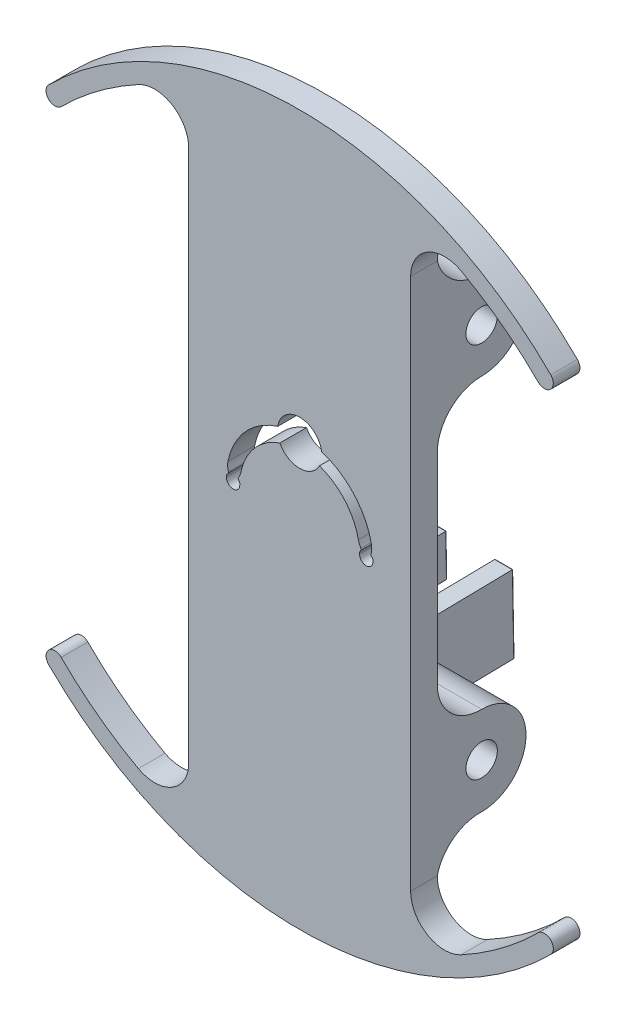
SolidWorks part; units mm, degrees
ref_plane "Front Plane" through (0, 0, 0) normal (0, 0, 1) x (1, 0, 0)
ref_plane "Top Plane" through (0, 0, 0) normal (0, 1, 0) x (1, 0, 0)
ref_plane "Right Plane" through (0, 0, 0) normal (1, 0, 0) x (0, 0, -1)
sketch "Sketch3" plane through (0, 0, 0) normal (0, 0, 1) x (1, 0, 0)
  line L0 (-35.921, -35.921) -> (-34.125, -34.125) construction
  line L1 (-15.875, -38.1) -> (0, -38.1) construction
  line L2 (-15.875, -38.1) -> (-15.875, 38.1)
  line L3 (-15.875, 38.1) -> (0, 38.1) construction
  line L4 (15.875, -38.1) -> (15.875, 38.1)
  line L5 (-15.875, -38.1) -> (15.875, 38.1) construction
  line L6 (-15.875, 38.1) -> (15.875, -38.1) construction
  line L7 (35.921, -35.921) -> (34.125, -34.125) construction
  line L8 (0, -50.8) -> (0, 50.8) construction
  line L9 (0, 38.1) -> (15.875, 38.1) construction
  line L10 (0, -38.1) -> (15.875, -38.1) construction
  line L11 (-34.125, -34.125) -> (-15.875, -15.875) construction
  line L12 (34.125, 34.125) -> (35.921, 35.921) construction
  line L13 (-15.875, -15.875) -> (0, 0) construction
  line L14 (15.875, -15.875) -> (0, 0) construction
  line L15 (-34.125, 34.125) -> (-35.921, 35.921) construction
  line L16 (34.125, -34.125) -> (15.875, -15.875) construction
  line L17 (0, 0) -> (-15.875, 15.875) construction
  line L18 (0, 0) -> (15.875, 15.875) construction
  line L19 (-15.875, 15.875) -> (-34.125, 34.125) construction
  line L20 (15.875, 15.875) -> (34.125, 34.125) construction
  arc A0 (-35.921, -35.921) -> (35.921, -35.921) centre (0, 0) ccw
  arc A1 (-34.125, -34.125) -> (-23.0827, -42.3818) centre (0, 0) ccw
  arc A2 (-15.875, 38.1) -> (-23.0827, 42.3818) centre (-20.7507, 38.1) ccw
  arc A3 (15.875, 38.1) -> (23.0827, 42.3818) centre (20.7507, 38.1) cw
  arc A4 (-15.875, -38.1) -> (-23.0827, -42.3818) centre (-20.7507, -38.1) cw
  arc A5 (15.875, -38.1) -> (23.0827, -42.3818) centre (20.7507, -38.1) ccw
  arc A6 (-35.921, 35.921) -> (-35.921, -35.921) centre (0, 0) ccw construction
  circle A7 centre (0, 0) radius 50.8 construction
  arc A8 (-34.125, 34.125) -> (-34.125, -34.125) centre (0, 0) ccw construction
  circle A9 centre (0, 0) radius 48.26 construction
  arc A10 (34.125, -34.125) -> (34.125, 34.125) centre (0, 0) ccw construction
  arc A11 (34.125, 34.125) -> (23.0827, 42.3818) centre (0, 0) ccw
  arc A12 (35.921, -35.921) -> (35.921, 35.921) centre (0, 0) ccw construction
  arc A13 (35.921, 35.921) -> (-35.921, 35.921) centre (0, 0) ccw
  arc A14 (0, 48.26) -> (-23.0827, 42.3818) centre (0, 0) ccw construction
  arc A15 (-23.0827, 42.3818) -> (-34.125, 34.125) centre (0, 0) ccw
  arc A16 (23.0827, 42.3818) -> (0, 48.26) centre (0, 0) ccw construction
  arc A17 (-23.0827, -42.3818) -> (0, -48.26) centre (0, 0) ccw construction
  arc A18 (23.0827, -42.3818) -> (34.125, -34.125) centre (0, 0) ccw
  arc A19 (0, -48.26) -> (23.0827, -42.3818) centre (0, 0) ccw construction
  arc A20 (-35.921, 35.921) -> (-34.125, 34.125) centre (-35.023, 35.023) ccw
  arc A21 (34.125, 34.125) -> (35.921, 35.921) centre (35.023, 35.023) ccw
  arc A22 (-35.921, -35.921) -> (-34.125, -34.125) centre (-35.023, -35.023) cw
  arc A23 (34.125, -34.125) -> (35.921, -35.921) centre (35.023, -35.023) cw
  point P0 (0, 0)
  point P13 (0, 0)
  point P16 (0, 0)
  point P18 (0, 0)
  dimension "D3" = 2.54
  dimension "D6" = 101.6
  dimension "D1" = 76.2
  dimension "D2" = 31.75
  dimension "D4" = 45
  dimension "D5" = 45
extrude "Main body" add sketch "Sketch3" along normal blind 3.81
sketch "Sketch5" plane through (15.875, 0, 0) normal (1, 0, 0) x (0, 0, -1)
  line L0 (0, 26.9938) -> (0, -26.9938)
  line L1 (0, -38.1) -> (0, 38.1) construction
  line L2 (0, 26.9938) -> (6.35, 26.9939) construction
  line L3 (6.35, 26.9939) -> (6.35, -26.9938) construction
  line L4 (6.35, -26.9938) -> (0, -26.9938) construction
  line L5 (0, 38.1) -> (0, 14.2939)
  line L6 (0, -14.2939) -> (0, -38.1)
  circle A0 centre (-0.0451, 26.9938) radius 0.0451
  arc A2 (6.35, 20.6439) -> (6.3413, 33.3438) centre (6.35, 26.9939) ccw
  arc A3 (6.0778, -33.338) -> (6.2617, -20.6445) centre (6.35, -26.9938) ccw
  arc A4 (6.35, 20.6439) -> (0, 14.2939) centre (6.3675, 14.2763) ccw
  arc A5 (6.3413, 33.3438) -> (0, 38.1) centre (6.1542, 39.6999) cw
  arc A6 (6.35, -20.6438) -> (0, -14.2939) centre (6.2623, -14.3815) cw
  arc A7 (6.35, -33.3439) -> (0, -38.1) centre (6.0797, -39.6) ccw
  arc A8 (6.3413, 33.3438) -> (0, 26.9938) centre (6.35, 26.9939) ccw construction
  arc A9 (0, 26.9938) -> (6.35, 20.6439) centre (6.35, 26.9939) ccw construction
  arc A10 (6.2617, -20.6445) -> (0, -26.9938) centre (6.35, -26.9938) ccw construction
  arc A11 (0, -26.9938) -> (6.0778, -33.338) centre (6.35, -26.9938) ccw construction
  point P5 (0, 0)
  line M6 (0, -38.1) -> (0, 38.1)
  dimension "D1" = 53.9877
  dimension "D2" = 6.35
  dimension "D3" = 12.7
  dimension "D4" = 12.7
extrude "Bosses/spacers" add sketch "Sketch5" against normal up to surface (31.75 mm away) contours A2 A5 L0 A4 M6 | A7 A3 A6 L6 M6 region at (15.875, 26.931, -5.3159) region at (15.875, -26.9385, -5.3244) up to face at (-15.875, 0, 1.905)
hole_wizard "#8 Clearance Hole1" positions "Sketch8" profile "Sketch7" hole size "#8" standard "ANSI Inch" end condition through all
sketch "Sketch8" plane through (15.875, 0, 0) normal (1, 0, 0) x (0, 0, -1)
  point P7 (6.35, 26.9939)
  point P10 (6.35, -26.8934)
sketch "Sketch7" plane through (15.875, 26.9939, -6.35) normal (0, 1, 0) x (0, 0, -1)
  line L0 (0, 0) -> (0, 52.168)
  line L1 (0, 52.168) -> (2.2479, 52.168)
  line L2 (2.2479, 52.168) -> (2.2479, 0)
  line L5 (2.2479, 0) -> (0, 0)
  line L11 (0, -6.35) -> (0, 107.95) construction
  dimension "Thru Hole Dia." = 4.4958
  dimension "Thru Hole Depth" = 52.168
sketch "Sketch26" plane through (0, 0, 0) normal (0, 0, -1) x (-1, 0, 0)
  line L6 (9.525, 0) -> (-9.525, 0) construction
  line L7 (15.875, -14.4692) -> (-15.875, -14.4692) construction
  line L8 (-15.875, -14.4692) -> (-15.875, 14.2939) construction
  line L9 (15.875, 14.2939) -> (15.875, -14.4692) construction
  line L15 (15.875, 14.2939) -> (15.875, -14.4692) construction
  line L16 (15.875, -14.4692) -> (-15.875, -14.4692) construction
  circle A0 centre (0, 9.525) radius 3.175
  arc A1 (9.525, 0) -> (-9.525, 0) centre (0, 0) ccw construction
  arc A2 (10.4775, 0) -> (-10.4775, 0) centre (0, 0) ccw
  arc A3 (8.5725, 0) -> (-8.5725, 0) centre (0, 0) ccw
  arc A4 (10.4775, 0) -> (8.5725, 0) centre (9.525, 0) cw
  arc A5 (-10.4775, 0) -> (-8.5725, 0) centre (-9.525, 0) ccw
  circle A6 centre (-9.525, 0) radius 0.9525 construction
  arc A7 (-8.5188, 0.9578) -> (-8.5607, 0.4492) centre (-8.5436, 0.7038) ccw
  arc A8 (-10.4266, 1.0318) -> (-10.4644, 0.5233) centre (-10.4486, 0.7778) cw
  circle A9 centre (9.525, 0) radius 0.9525 construction
  arc A10 (10.4268, 1.0292) -> (10.4645, 0.5226) centre (10.4487, 0.7761) ccw
  arc A11 (8.5192, 0.9548) -> (8.5608, 0.4485) centre (8.5437, 0.7019) cw
  dimension "D1" = 6.35
  dimension "D5" = 0.254
  dimension "D2" = 0.9525
  dimension "D4" = 6.35
  dimension "D6" = 0.254
  dimension "D7" = 0.254
  dimension "D8" = 0.254
  dimension "D3" = 0.9525
sketch "Sketch28" plane through (0, 0.2841, -16.2788) normal (0, -0.0175, 0.9998) x (1, 0, 0)
  line L0 (-15.875, -20.7515) -> (-15.875, -33.4506) construction
  line L1 (-15.875, -20.7515) -> (-15.875, -33.4506) construction
  line L2 (-9.625, -21.9608) -> (-9.625, -28.0169)
  line L3 (-15.875, -33.0969) -> (-0.085, -33.0969)
  line L4 (-15.875, -33.0969) -> (-15.875, -21.9608)
  line L5 (-15.875, -21.9608) -> (-0.085, -21.9608)
  line L6 (-0.085, -33.0969) -> (-0.085, -21.9608)
  line L7 (-9.625, -28.0169) -> (-15.875, -28.0169)
  line L8 (-15.875, -30.5569) -> (-2.575, -30.5569)
  line L9 (-2.575, -30.5569) -> (-2.625, -24.9594)
  line L10 (-2.625, -24.5596) -> (-2.625, -21.9608)
  line L16 (-2.625, -24.9594) -> (-2.575, -24.9594)
  line L17 (-2.625, -30.0571) -> (-2.625, -24.9594)
  line L18 (-9.625, -30.5569) -> (-3.125, -30.5569)
  line L19 (-9.625, -21.3611) -> (-9.625, -30.5569)
  line L20 (-8.925, -21.3611) -> (-9.625, -21.3611)
  line L21 (-8.925, -21.9608) -> (-8.925, -21.3611)
  line L22 (-7.225, -21.9608) -> (-8.925, -21.9608)
  line L23 (-7.225, -23.8599) -> (-7.225, -21.9608)
  line L24 (-6.025, -23.8599) -> (-7.225, -23.8599)
  line L25 (-6.025, -21.9608) -> (-6.025, -23.8599)
  line L26 (-3.625, -21.9608) -> (-6.025, -21.9608)
  line L27 (-3.625, -21.3611) -> (-3.625, -21.9608)
  line L28 (-2.725, -21.3611) -> (-3.625, -21.3611)
  line L29 (-2.625, -24.5596) -> (-2.625, -21.461)
  line L30 (-2.375, -24.5596) -> (-2.625, -24.5596)
  line L31 (-2.375, -24.7595) -> (-2.375, -24.5596)
  line L32 (-2.625, -24.9594) -> (-2.575, -24.9594)
  line L33 (-2.625, -30.0571) -> (-2.625, -24.9594) construction
  line L34 (-9.625, -30.5569) -> (-3.125, -30.5569) construction
  line L35 (-9.625, -21.3611) -> (-9.625, -30.5569) construction
  line L36 (-8.925, -21.3611) -> (-9.625, -21.3611) construction
  line L37 (-8.925, -21.9608) -> (-8.925, -21.3611) construction
  line L38 (-7.225, -21.9608) -> (-8.925, -21.9608) construction
  line L39 (-7.225, -23.8599) -> (-7.225, -21.9608) construction
  line L40 (-6.025, -23.8599) -> (-7.225, -23.8599) construction
  line L41 (-6.025, -21.9608) -> (-6.025, -23.8599) construction
  line L42 (-3.625, -21.9608) -> (-6.025, -21.9608) construction
  line L43 (-3.625, -21.3611) -> (-3.625, -21.9608) construction
  line L44 (-2.725, -21.3611) -> (-3.625, -21.3611) construction
  line L45 (-2.625, -24.5596) -> (-2.625, -21.461) construction
  line L46 (-2.375, -24.5596) -> (-2.625, -24.5596)
  line L47 (-2.375, -24.7595) -> (-2.375, -24.5596)
  ellipse E3 centre (-3.125, -30.0571) end of major axis (-2.625, -30.0571) minor radius 0.4998 (-3.125, -30.5569) -> (-2.625, -30.0571) ccw
  ellipse E4 centre (-2.725, -21.461) end of major axis (-2.625, -21.461) minor radius 0.1 (-2.625, -21.461) -> (-2.725, -21.3611) ccw
  ellipse E5 centre (-2.575, -24.7595) end of major axis (-2.775, -24.7595) minor radius 0.1999 (-2.575, -24.9594) -> (-2.375, -24.7595) ccw
  ellipse E6 centre (-3.125, -30.0571) end of major axis (-3.625, -30.0571) minor radius 0.4998 (-3.125, -30.5569) -> (-2.625, -30.0571) ccw construction
  ellipse E7 centre (-2.725, -21.461) end of major axis (-2.625, -21.461) minor radius 0.1 (-2.625, -21.461) -> (-2.725, -21.3611) ccw construction
  ellipse E8 centre (-2.575, -24.7595) end of major axis (-2.775, -24.7595) minor radius 0.1999 (-2.575, -24.9594) -> (-2.375, -24.7595) ccw
  ellipse M20 centre (-2.575, -24.6198) end of major axis (-2.575, -24.4198) minor radius 0.2 (-2.575, -24.8199) -> (-2.375, -24.6198) ccw
  line M21 (-2.375, -24.6198) -> (-2.375, -24.4198)
  line M22 (-2.375, -24.4198) -> (-2.625, -24.4198)
  line M23 (-2.625, -24.4198) -> (-2.625, -21.3193)
  line M28 (-6.025, -21.8194) -> (-6.025, -23.7197)
  line M29 (-6.025, -23.7197) -> (-7.225, -23.7197)
  line M30 (-7.225, -23.7197) -> (-7.225, -21.8194)
  line M34 (-9.625, -21.2193) -> (-9.625, -30.4207)
  line M35 (-9.625, -30.4207) -> (-3.125, -30.4207)
  ellipse M36 centre (-3.125, -29.9207) end of major axis (-3.125, -29.4206) minor radius 0.5 (-3.125, -30.4207) -> (-2.625, -29.9207) ccw
  line M37 (-2.625, -29.9207) -> (-2.625, -24.8199)
  line M38 (-2.625, -24.8199) -> (-2.575, -24.8199)
  dimension "D2" = 2.54
  dimension "D3" = 2.54
  dimension "D4" = 2.54
  dimension "D1" = 0
extrude "Hot wire cutter base" add sketch "Sketch28" along normal up to surface (6.6744 mm away) contours E8 L32 L9 L8 L4 L3 L6 L5 L47 M23 M22 M21 | L32 E8 L47 M20 M38 M37 | L46 L10 M21 M22 | L46 L10 L5 M21 M23 M28 M29 M30 M34 M35 M36 M37 M38 M20 | L8 L9 L7 L4 M37 M36 M35 M34 | L7 L5 L4 M34 | L5 M30 M29 M28 | L4 L3 L6 L5 region at (-6.1046, -26.0285, -16.7381) region at (-12.75, -24.7009, -16.7149) region at (-12.75, -28.9983, -16.79) region at (-6.1249, -30.1923, -16.8108) region at (-6.625, -22.5526, -16.6774) region at (-12.75, -30.4612, -16.8155) region at (-6.625, -23.502, -16.694) region at (-2.7317, -30.1615, -16.8103) region at (-2.5, -24.5674, -16.7126) region at (-2.5, -24.2018, -16.7062) up to face at (0, -26.9939, -9.525)
extrude "Hot wire cutter fingers" add sketch "Sketch28<3>" against normal blind 10.16 contours E8 L32 L9 L8 L4 L3 L6 L5 L47 M23 M22 M21 | L7 L5 L4 M34 region at (-12.75, -24.7009, -16.7149) region at (-12.75, -30.4612, -16.8155)
sketch "Sketch28<3>" plane through (0, 0.2841, -16.2788) normal (0, -0.0175, 0.9998) x (1, 0, 0) same geometry as "Sketch28"
fillet "Hot wire cutter fillet" radius 0.127 14 edges at (-9.625, -24.5236, -26.8734) (-12.75, -21.496, -26.8205) (-15.875, -24.5236, -26.8734) (-12.75, -27.5511, -26.9262) (-2.6, -27.2924, -26.9217) (-9.225, -30.0907, -26.9706) (-15.875, -31.3605, -26.9927) (-7.98, -32.6304, -27.0149) (-0.085, -27.0632, -26.9177) (-1.355, -21.496, -26.8205) (-2.625, -22.7253, -26.842) (-2.5, -23.9546, -26.8635) (-2.375, -24.1245, -26.8664) (-2.4336, -24.4356, -26.8719)
extrude "Monofilament slot" cut sketch "Sketch26" against normal through all contours A2 A0 | A3 A0 A2 | A0 A3 | A3 A11 A4 A2 A10 A0 | A2 A8 A5 A3 A7 A0 region at (0, 9.3688, 0) region at (-7.4018, 4.9128, 0) region at (0, 11.3064, 0) region at (0, 7.5624, 0) region at (7.4016, 4.9131, 0)
fillet "Fillet4" radius 2.54 4 edges at (-10.4268, 1.0292, 1.905) (-8.5192, 0.9548, 1.905) (10.4266, 1.0318, 1.905) (8.5188, 0.9578, 1.905)
fillet "Fillet5" radius 0.508 4 edges at (-8.5608, 0.4485, 1.905) (-10.4645, 0.5226, 1.905) (10.4644, 0.5233, 1.905) (8.5607, 0.4492, 1.905)
sketch "Sketch27" plane through (0, 0, 0) normal (0, 0, -1) x (-1, 0, 0)
  line L0 (7.62, 0) -> (-7.62, 0) construction
  text T0 "> <" font "Century Gothic" height 6.35
  point P4 (0, 0)
  dimension "D1" = 15.24
extrude "Cut-Extrude1 eyes" cut sketch "Sketch27" against normal blind 0.508
